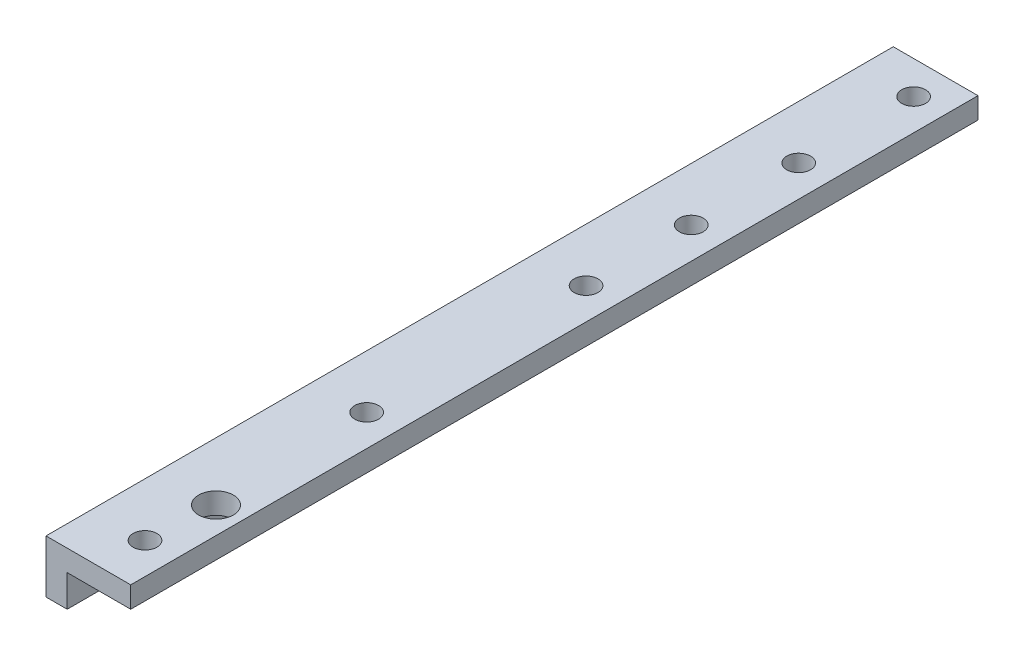
SolidWorks part; units mm, degrees
material "Plain Carbon Steel"
ref_plane "Front Plane" through (0, 0, 0) normal (0, 0, 1) x (1, 0, 0)
ref_plane "Top Plane" through (0, 0, 0) normal (0, 1, 0) x (1, 0, 0)
ref_plane "Right Plane" through (0, 0, 0) normal (1, 0, 0) x (0, 0, -1)
sketch "Sketch1" plane through (0, 0, 0) normal (0, 0, 1) x (1, 0, 0)
  line L0 (0, 0) -> (0, -10)
  line L5 (0, -10) -> (4, -10)
  line L6 (4, -10) -> (4, -4)
  line L11 (4, -4) -> (16, -4)
  line L12 (16, -4) -> (16, 0)
  line L13 (16, 0) -> (0, 0)
  point P0 (0, 0)
  dimension "D1" = 16
  dimension "D2" = 10
  dimension "D3" = 4
  dimension "D4" = 4
extrude "Boss-Extrude1" add sketch "Sketch1" along normal blind 160
sketch "Sketch2" plane through (4, 0, 0) normal (1, 0, 0) x (0, 0, -1)
  line L0 (-120.4489, -8) -> (-160, -8)
  line L2 (-120.4489, -10) -> (-160, -10)
  line L4 (-160, -10) -> (-160, -8)
  line L6 (-120.4489, -10) -> (-120.4489, -8)
  point P3 (-140.2245, -8)
extrude "Cut-Extrude1" [suppressed] cut sketch "Sketch2" against normal up to surface (4 mm away) up to face at (0, -5, 80)
hole_wizard "M4 Clearance Hole1" positions "Sketch3" profile "Sketch4" hole size "M4" standard "ISO" end condition through all
sketch "Sketch3" plane through (0, -4, 0) normal (0, -1, 0) x (-1, 0, 0)
  point P0 (-10.0724, -6.2281)
  point P2 (-10.0724, -27.9379)
  point P4 (-10.0724, -48.2215)
  point P6 (-10.0724, -68.0876)
  point P8 (-10.0724, -109.5175)
  point P10 (-10.0724, -151.3766)
sketch "Sketch4" plane through (10.0724, -4, 6.2281) normal (1, 0, 0) x (0, 0, -1)
  line L0 (0, 0) -> (0, 4)
  line L1 (0, 4) -> (2.25, 4)
  line L2 (2.25, 4) -> (2.25, 0)
  line L5 (2.25, 0) -> (0, 0)
  line L11 (0, -6.35) -> (0, 107.95) construction
  dimension "Thru Hole Dia." = 4.5
  dimension "Thru Hole Depth" = 4
sketch "Sketch5" plane through (0, -4, 0) normal (0, -1, 0) x (1, 0, 0)
  circle A0 centre (11, 138.8979) radius 3.275
extrude "Cut-Extrude2" cut sketch "Sketch5" against normal blind 10
